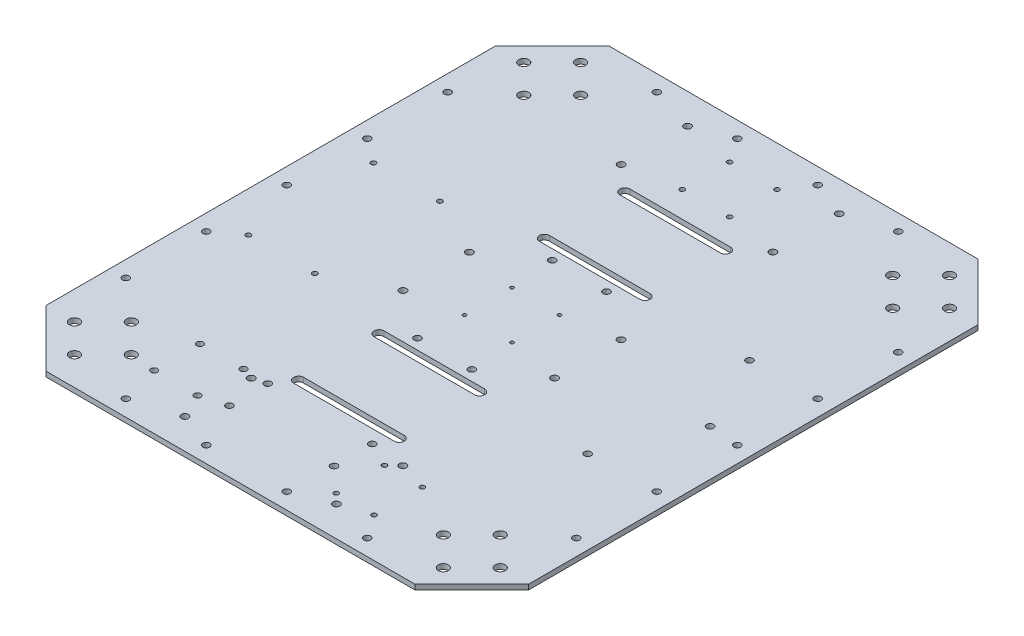
SolidWorks part; units mm, degrees
ref_plane "Front Plane" through (0, 0, 0) normal (0, 0, 1) x (1, 0, 0)
ref_plane "Top Plane" through (0, 0, 0) normal (0, 1, 0) x (1, 0, 0)
ref_plane "Right Plane" through (0, 0, 0) normal (1, 0, 0) x (0, 0, -1)
sketch "Sketch1" plane through (0, 0, 0) normal (0, 1, 0) x (1, 0, 0)
  line L0 (-121.2861, 87.138) -> (-85.365, 123.059)
  line L1 (-121.2861, 123.059) -> (183.5139, 123.059)
  line L2 (-121.2861, 123.059) -> (-121.2861, -232.541)
  line L3 (-121.2861, -232.541) -> (183.5139, -232.541)
  line L4 (183.5139, 123.059) -> (183.5139, -232.541)
  line L5 (31.1139, 95.069) -> (31.1139, -294.9418) construction
  line L6 (-146.0448, -54.741) -> (218.038, -54.741) construction
  line L7 (183.5139, 87.138) -> (147.5929, 123.059)
  line L8 (183.5139, -196.62) -> (147.5929, -232.541)
  line L9 (-121.2861, -196.62) -> (-85.365, -232.541)
  circle A0 centre (-16.7651, 104.009) radius 2.2225
  circle A1 centre (78.9929, 104.009) radius 2.2225
  circle A2 centre (-16.7651, 62.099) radius 2.2225
  circle A3 centre (78.9929, 62.099) radius 2.2225
  circle A4 centre (-16.7651, -171.581) radius 2.2225
  circle A5 centre (78.9929, -171.581) radius 2.2225
  circle A6 centre (78.9929, -213.491) radius 2.2225
  circle A7 centre (-16.7651, -213.491) radius 2.2225
  circle A8 centre (-16.7651, -33.786) radius 2.2225
  circle A9 centre (78.9929, -33.786) radius 2.2225
  circle A10 centre (78.9929, -75.696) radius 2.2225
  circle A11 centre (-16.7651, -75.696) radius 2.2225
  point P8 (31.1139, 123.059)
  point P11 (-121.2861, -54.741)
  dimension "D6" = 95.758
  dimension "D13" = 4.445
  dimension "D1" = 304.8
  dimension "D2" = 355.6
  dimension "D3" = 45
  dimension "D4" = 50.8
  dimension "D5" = 41.91
  dimension "D7" = 104.521
  dimension "D8" = 19.05
  dimension "D9" = 41.91
  dimension "D10" = 20.955
  dimension "D11" = 95.758
  dimension "D12" = 47.879
extrude "Boss-Extrude1" add sketch "Sketch1" along normal blind 3.175 contours L2 L9 L3 L8 L4 L7 L1 L0 region at (31.1139, 0, 54.741)
sketch "Sketch2" plane through (0, 3.175, 0) normal (0, 1, 0) x (1, 0, 0)
  line L0 (31.1139, 123.059) -> (31.1139, -287.8465) construction
  line L1 (-85.365, 123.059) -> (147.5929, 123.059) construction
  line L2 (183.5139, -54.741) -> (-158.2106, -54.741) construction
  line L3 (183.5139, 87.138) -> (183.5139, -196.62) construction
  circle A0 centre (13.8419, -12.069) radius 2.159
  circle A1 centre (48.1319, -12.069) radius 2.159
  circle A2 centre (13.8419, -97.159) radius 2.159
  circle A3 centre (48.1319, -97.159) radius 2.159
  dimension "D5" = 4.318
  dimension "D6" = 4.318
  dimension "D7" = 4.318
  dimension "D8" = 4.318
  dimension "D1" = 17.272
  dimension "D2" = 34.29
  dimension "D3" = 85.09
  dimension "D4" = 42.672
extrude "Cut-Extrude1" cut sketch "Sketch2" against normal through all
sketch "Sketch4" plane through (0, 3.175, 0) normal (0, 1, 0) x (1, 0, 0)
  line L0 (-0.6361, 48.256) -> (62.8639, 48.256) construction
  line L1 (-0.6361, 51.431) -> (62.8639, 51.431)
  line L2 (-0.6361, 45.081) -> (62.8639, 45.081)
  line L3 (-0.6361, -2.544) -> (62.8639, -2.544) construction
  line L4 (-0.6361, 0.631) -> (62.8639, 0.631)
  line L5 (-0.6361, -5.719) -> (62.8639, -5.719)
  line L6 (31.1139, 123.059) -> (31.1139, -75.2432) construction
  line L7 (-85.365, 123.059) -> (147.5929, 123.059) construction
  line L8 (-121.2861, -54.741) -> (257.7387, -54.741) construction
  line L9 (-121.2861, 87.138) -> (-121.2861, -196.62) construction
  line L10 (31.1139, -232.541) -> (31.1139, -34.2388) construction
  line L11 (-0.6361, -106.938) -> (62.8639, -106.938) construction
  line L12 (-0.6361, -110.113) -> (62.8639, -110.113)
  line L13 (-0.6361, -103.763) -> (62.8639, -103.763)
  line L14 (-0.6361, -157.738) -> (62.8639, -157.738) construction
  line L15 (-0.6361, -160.913) -> (62.8639, -160.913)
  line L16 (-0.6361, -154.563) -> (62.8639, -154.563)
  arc A0 (-0.6361, 51.431) -> (-0.6361, 45.081) centre (-0.6361, 48.256) ccw
  arc A1 (62.8639, 45.081) -> (62.8639, 51.431) centre (62.8639, 48.256) ccw
  arc A2 (-0.6361, 0.631) -> (-0.6361, -5.719) centre (-0.6361, -2.544) ccw
  arc A3 (62.8639, -5.719) -> (62.8639, 0.631) centre (62.8639, -2.544) ccw
  circle A4 centre (48.1319, -12.069) radius 2.159 construction
  arc A5 (-0.6361, -110.113) -> (-0.6361, -103.763) centre (-0.6361, -106.938) cw
  arc A6 (62.8639, -103.763) -> (62.8639, -110.113) centre (62.8639, -106.938) cw
  arc A7 (-0.6361, -160.913) -> (-0.6361, -154.563) centre (-0.6361, -157.738) cw
  arc A8 (62.8639, -154.563) -> (62.8639, -160.913) centre (62.8639, -157.738) cw
  point P2 (31.1139, 48.256)
  point P7 (31.1139, -2.544)
  point P28 (31.1139, -106.938)
  point P35 (31.1139, -157.738)
  dimension "D1" = 63.5
  dimension "D2" = 63.5
  dimension "D3" = 6.35
  dimension "D4" = 6.35
  dimension "D5" = 44.45
  dimension "D6" = 6.35
extrude "Cut-Extrude2" cut sketch "Sketch4" against normal through all
sketch "Sketch7" plane through (0, 3.175, 0) normal (0, 1, 0) x (1, 0, 0)
  line L0 (31.1139, 123.059) -> (31.1139, -19.2461) construction
  line L3 (-85.365, 123.059) -> (147.5929, 123.059) construction
  circle A0 centre (16.1279, 67.687) radius 1.524
  circle A1 centre (46.0999, 67.687) radius 1.524
  circle A2 centre (16.1279, 97.659) radius 1.524
  circle A3 centre (46.0999, 97.659) radius 1.524
  dimension "D1" = 3.048
  dimension "D2" = 3.048
  dimension "D4" = 14.986
  dimension "D3" = 29.972
  dimension "D5" = 25.4
extrude "Cut-Extrude3" cut sketch "Sketch7" against normal through all
sketch "Sketch8" plane through (0, 3.175, 0) normal (0, 1, 0) x (1, 0, 0)
  line L0 (-85.365, -232.541) -> (147.5929, -232.541) construction
  line L1 (183.5139, 87.138) -> (183.5139, -196.62) construction
  circle A0 centre (73.0239, -207.649) radius 1.524
  circle A1 centre (73.0239, -177.169) radius 1.524
  circle A2 centre (96.8999, -207.649) radius 1.524
  circle A3 centre (96.8999, -177.169) radius 1.524
  dimension "D1" = 3.048
  dimension "D2" = 30.48
  dimension "D3" = 23.876
  dimension "D4" = 24.892
  dimension "D5" = 86.614
extrude "Cut-Extrude4" cut sketch "Sketch8" against normal through all and the other way through all
sketch "Sketch9" plane through (0, 0, 0) normal (0, -1, 0) x (-1, 0, 0)
  line L0 (85.365, -232.541) -> (-147.5929, -232.541) construction
  line L1 (121.2861, 87.138) -> (121.2861, -196.62) construction
  circle A0 centre (51.6494, -197.9691) radius 2.032
  circle A1 centre (24.2174, -197.9691) radius 2.032
  circle A2 centre (51.6494, -169.0131) radius 2.032
  circle A3 centre (24.2174, -169.0131) radius 2.032
  dimension "D1" = 4.064
  dimension "D2" = 27.432
  dimension "D3" = 28.956
  dimension "D4" = 34.5719
  dimension "D5" = 69.6366
extrude "Cut-Extrude5" cut sketch "Sketch9" against normal through all
sketch "Sketch10" plane through (0, 0, 0) normal (0, -1, 0) x (1, 0, 0)
  line L0 (-85.365, 232.541) -> (147.5929, 232.541) construction
  line L2 (-121.2861, -87.138) -> (-121.2861, 196.62) construction
  circle A0 centre (-8.5761, 193.4758) radius 2.159
  circle A1 centre (57.4639, 193.4758) radius 2.159
  circle A2 centre (-8.5761, 169.3458) radius 2.159
  circle A3 centre (57.4639, 169.3458) radius 2.159
  dimension "D1" = 4.318
  dimension "D2" = 66.04
  dimension "D4" = 39.0652
  dimension "D6" = 4.318
  dimension "D7" = 4.318
  dimension "D8" = 4.318
  dimension "D3" = 24.13
  dimension "D5" = 112.71
extrude "Cut-Extrude6" cut sketch "Sketch10" against normal through all
sketch "Sketch12" plane through (0, 0, 0) normal (0, -1, 0) x (1, 0, 0)
  line L0 (-121.2861, 54.741) -> (204.2138, 54.741) construction
  line L1 (-121.2861, -87.138) -> (-121.2861, 196.62) construction
  circle A0 centre (-95.8861, 94.216) radius 1.575
  circle A1 centre (-95.8861, 15.266) radius 1.575
  circle A2 centre (-53.9361, 15.266) radius 1.575
  circle A3 centre (-53.9361, 94.216) radius 1.575
  dimension "D1" = 3.15
  dimension "D2" = 3.15
  dimension "D3" = 3.15
  dimension "D4" = 3.15
  dimension "D5" = 78.95
  dimension "D6" = 39.475
  dimension "D7" = 41.95
  dimension "D8" = 25.4
extrude "Cut-Extrude7" cut sketch "Sketch12" against normal through all
sketch "Sketch13" plane through (0, 0, 0) normal (0, -1, 0) x (1, 0, 0)
  line L0 (31.1139, -123.059) -> (31.1139, 261.4711) construction
  line L1 (-85.365, -123.059) -> (147.5929, -123.059) construction
  line L2 (-121.2861, 54.741) -> (239.2508, 54.741) construction
  line L3 (-121.2861, -87.138) -> (-121.2861, 196.62) construction
  circle A0 centre (16.1139, 69.741) radius 1.1
  circle A1 centre (16.1139, 39.741) radius 1.1
  circle A2 centre (46.1139, 39.741) radius 1.1
  circle A3 centre (46.1139, 69.741) radius 1.1
  dimension "D1" = 2.2
  dimension "D2" = 2.2
  dimension "D3" = 30
  dimension "D4" = 15
  dimension "D5" = 15
extrude "Cut-Extrude8" cut sketch "Sketch13" against normal through all
sketch "Sketch14" plane through (0, 0, 0) normal (0, -1, 0) x (1, 0, 0)
  line L0 (31.1139, 232.541) -> (31.1139, -154.5354) construction
  line L1 (-85.365, 232.541) -> (147.5929, 232.541) construction
  line L2 (-121.2861, 54.741) -> (331.9066, 54.741) construction
  line L3 (-121.2861, -87.138) -> (-121.2861, 196.62) construction
  line L4 (-85.365, 214.5805) -> (-103.3255, 196.62) construction
  line L5 (-103.3255, 196.62) -> (-85.365, 178.6595) construction
  line L6 (-85.365, 178.6595) -> (-67.4045, 196.62) construction
  line L7 (-67.4045, 196.62) -> (-85.365, 214.5805) construction
  line L8 (-121.2861, 196.62) -> (-85.365, 232.541) construction
  line L9 (-103.3255, 214.5805) -> (-48.3665, 159.6215) construction
  circle A0 centre (-103.3255, 196.62) radius 3.175
  circle A1 centre (-85.365, 214.5805) radius 3.175
  circle A2 centre (-85.365, 178.6595) radius 3.175
  circle A3 centre (-67.4045, 196.62) radius 3.175
  circle A4 centre (129.6324, 196.62) radius 3.175
  circle A5 centre (147.5929, 178.6595) radius 3.175
  circle A6 centre (165.5534, 196.62) radius 3.175
  circle A7 centre (147.5929, 214.5805) radius 3.175
  circle A8 centre (-85.365, -105.0985) radius 3.175
  circle A9 centre (-103.3255, -87.138) radius 3.175
  circle A10 centre (-85.365, -69.1774) radius 3.175
  circle A11 centre (-67.4045, -87.138) radius 3.175
  circle A12 centre (165.5534, -87.138) radius 3.175
  circle A13 centre (147.5929, -69.1774) radius 3.175
  circle A14 centre (147.5929, -105.0985) radius 3.175
  circle A15 centre (129.6324, -87.138) radius 3.175
  dimension "D3" = 6.35
  dimension "D4" = 6.35
  dimension "D5" = 6.35
  dimension "D6" = 6.35
  dimension "D2" = 12.7
  dimension "D7" = 90
  dimension "D8" = 25.4
  dimension "D9" = 25.4
  dimension "D10" = 12.7
  dimension "D11" = 90
extrude "Cut-Extrude9" cut sketch "Sketch14" against normal through all
sketch "Sketch15" plane through (0, 0, 0) normal (0, -1, 0) x (1, 0, 0)
  line L0 (31.1139, 232.541) -> (31.1139, 125.875) construction
  line L1 (-85.365, 232.541) -> (147.5929, 232.541) construction
  line L2 (-121.2861, 54.741) -> (75.4631, 54.741) construction
  line L3 (-121.2861, -87.138) -> (-121.2861, 196.62) construction
  circle A0 centre (5.7139, 222.381) radius 2.159
  circle A1 centre (-45.0861, 222.381) radius 2.159
  circle A2 centre (-111.1261, 54.741) radius 2.159
  circle A3 centre (-111.1261, 105.541) radius 2.159
  circle A4 centre (-111.1261, 156.341) radius 2.159
  circle A5 centre (173.3539, 156.341) radius 2.159
  circle A6 centre (173.3539, 105.541) radius 2.159
  circle A7 centre (173.3539, 54.741) radius 2.159
  circle A8 centre (107.3139, 222.381) radius 2.159
  circle A9 centre (56.5139, 222.381) radius 2.159
  circle A10 centre (56.5139, -112.899) radius 2.159
  circle A11 centre (107.3139, -112.899) radius 2.159
  circle A12 centre (173.3539, 3.941) radius 2.159
  circle A13 centre (173.3539, -46.859) radius 2.159
  circle A14 centre (-111.1261, -46.859) radius 2.159
  circle A15 centre (-111.1261, 3.941) radius 2.159
  circle A16 centre (-45.0861, -112.899) radius 2.159
  circle A17 centre (5.7139, -112.899) radius 2.159
  dimension "D3" = 4.318
  dimension "D4" = 4.318
  dimension "D8" = 4.318
  dimension "D9" = 4.318
  dimension "D10" = 4.318
  dimension "D1" = 25.4
  dimension "D2" = 50.8
  dimension "D5" = 10.16
  dimension "D6" = 50.8
  dimension "D7" = 50.8
  dimension "D11" = 10.16
extrude "Cut-Extrude10" cut sketch "Sketch15" against normal through all
sketch "Sketch16" plane through (0, 0, 0) normal (0, -1, 0) x (-1, 0, 0)
  line L1 (-97.5856, -99.6794) -> (-147.4656, -99.6794)
  line L2 (-97.5856, -99.6794) -> (-97.5856, -11.5294)
  line L3 (-97.5856, -11.5294) -> (-147.4656, -11.5294)
  line L4 (-147.4656, -99.6794) -> (-147.4656, -11.5294)
  circle A0 centre (-130.8656, -106.6794) radius 2.159
  circle A1 centre (-130.8656, -4.5294) radius 2.159
  circle A2 centre (-154.4656, -53.0294) radius 2.159
  dimension "D3" = 7
  dimension "D4" = 7
  dimension "D5" = 7
  dimension "D6" = 16.6
  dimension "D7" = 16.6
  dimension "D8" = 46.65
  dimension "D9" = 4.318
  dimension "D10" = 4.318
  dimension "D11" = 4.318
  dimension "D1" = 88.15
  dimension "D2" = 49.88
extrude "Cut-Extrude11" cut sketch "Sketch16" against normal through all contours A2 | A0 | A1
